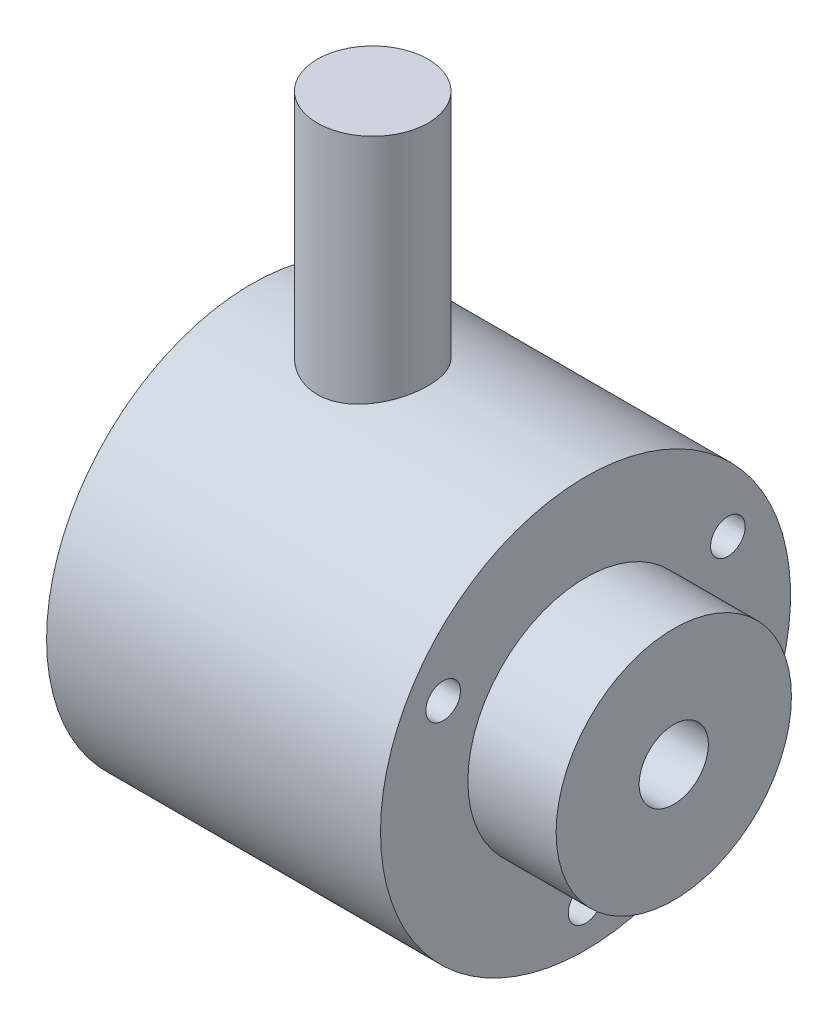
SolidWorks part; units mm, degrees
ref_plane "Plan de face" through (0, 0, 0) normal (0, 0, 1) x (1, 0, 0)
ref_plane "Plan de dessus" through (0, 0, 0) normal (0, 1, 0) x (1, 0, 0)
ref_plane "Plan de droite" through (0, 0, 0) normal (1, 0, 0) x (0, 0, -1)
sketch "Esquisse1" plane through (0, 0, 0) normal (0, 0, 1) x (1, 0, 0)
  line L0 (0, 0) -> (24.4, 0)
  line L1 (24.4, 0) -> (24.4, 6.8)
  line L2 (24.4, 6.8) -> (19.3, 6.8)
  line L3 (19.3, 6.8) -> (19.3, 11.85)
  line L4 (19.3, 11.85) -> (0, 11.85)
  line L5 (0, 11.85) -> (0, 0)
  dimension "D1" = 11.85
  dimension "D2" = 19.3
  dimension "D3" = 6.8
  dimension "D4" = 5.1
revolve "Révolution2" add sketch "Esquisse1" angle 360 about L0
sketch "Esquisse2" plane through (0, 0, 0) normal (0, 1, 0) x (1, 0, 0)
  line L0 (0, 11.85) -> (0, -11.85) construction
  circle A0 centre (7, 0) radius 3.2
  dimension "D1" = 6.4
  dimension "D2" = 7
extrude "Boss.-Extru.1" add sketch "Esquisse2" along normal blind 25
sketch "Esquisse3" plane through (24.4, 0, 0) normal (1, 0, 0) x (0, 0, -1)
  circle A0 centre (0, 0) radius 2
  dimension "D1" = 4
extrude "Enlèv. mat.-Extru.1" cut sketch "Esquisse3" against normal blind 14
ref_axis "Axe2" through (41.0663, 0, 0) along (-1, 0, 0)
sketch "Esquisse4" plane through (19.3, 0, 0) normal (1, 0, 0) x (0, 0, -1)
  line L0 (0, 13.42) -> (0, -13.42) construction
  circle A0 centre (0, -9.5) radius 1
  circle A1 centre (0, 0) radius 11.85 construction
  circle A2 centre (-8.2272, 4.75) radius 1
  circle A3 centre (8.2272, 4.75) radius 1
  point P2 (0, -11.85)
  dimension "D1" = 2
  dimension "D2" = 60
  dimension "D3" = 60
  dimension "D4" = 9.5
  dimension "D5" = 9.5
extrude "Enlèv. mat.-Extru.2" cut sketch "Esquisse4" against normal blind 4
